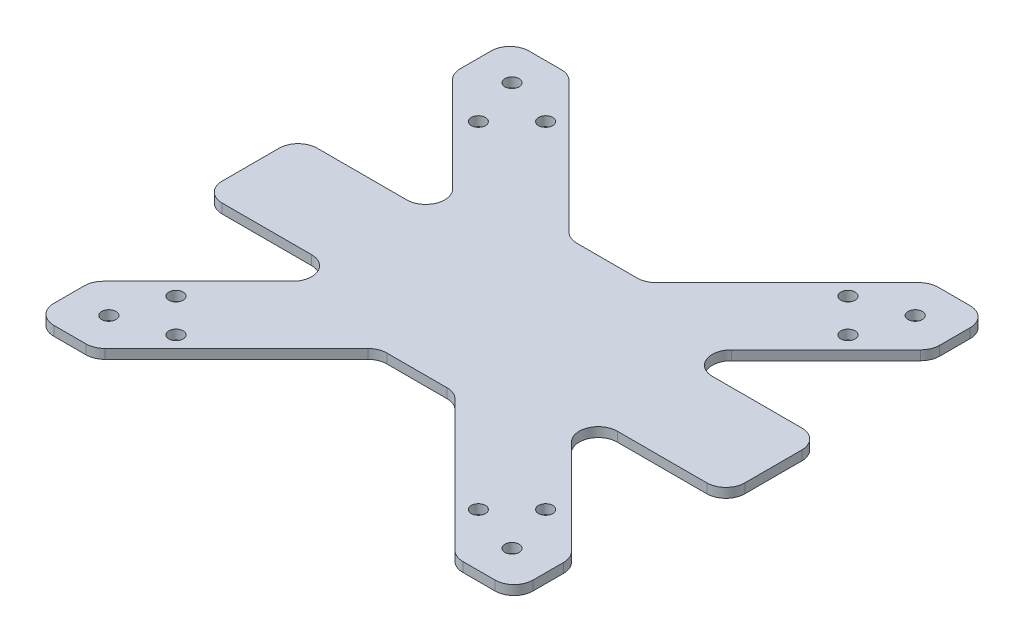
SolidWorks part; units mm, degrees
material "Thornel Mat VMA"
ref_plane "前视基准面" through (0, 0, 0) normal (0, 0, 1) x (1, 0, 0)
ref_plane "上视基准面" through (0, 0, 0) normal (0, 1, 0) x (1, 0, 0)
ref_plane "右视基准面" through (0, 0, 0) normal (1, 0, 0) x (0, 0, -1)
other "Configuration Table"
sketch "草图1" plane through (0, 0, 0) normal (0, 1, 0) x (1, 0, 0)
  line L1 (-60, -50) -> (60, -50)
  line L2 (-60, -50) -> (-60, 50)
  line L3 (-60, 50) -> (60, 50)
  line L4 (60, -50) -> (60, 50)
  line L5 (-60, -50) -> (60, 50) construction
  line L6 (-60, 50) -> (60, -50) construction
  point P0 (0, 0)
  dimension "D1" = 120
  dimension "D2" = 100
extrude "凸台-拉伸1" add sketch "草图1" along normal blind 2
sketch "草图3" plane through (0, 2, 0) normal (0, 1, 0) x (1, 0, 0)
  line L0 (-1000, 0) -> (49000, 0) construction
  line L1 (-42.4264, 42.4264) -> (0, 0) construction
  line L2 (-42.9749, 27.7358) -> (35312.3642, 35383.0749) construction
  line L3 (0, -1000) -> (0, 49000) construction
  circle A0 centre (0, 0) radius 60 construction
  circle A1 centre (-42.4264, 42.4264) radius 1.5
  circle A2 centre (-31.8198, 38.8909) radius 1.5
  circle A3 centre (-38.8909, 31.8198) radius 1.5
  circle A4 centre (-31.8198, -38.8909) radius 1.5
  circle A5 centre (-38.8909, -31.8198) radius 1.5
  circle A6 centre (-42.4264, -42.4264) radius 1.5
  circle A7 centre (31.8198, 38.8909) radius 1.5
  circle A8 centre (38.8909, 31.8198) radius 1.5
  circle A9 centre (42.4264, 42.4264) radius 1.5
  circle A10 centre (31.8198, -38.8909) radius 1.5
  circle A11 centre (42.4264, -42.4264) radius 1.5
  circle A12 centre (38.8909, -31.8198) radius 1.5
  dimension "D1" = 120
  dimension "D3" = 3
  dimension "D6" = 3
  dimension "D7" = 3
  dimension "D8" = 5
  dimension "D9" = 5
  dimension "D2" = 45
  dimension "D4" = 90
  dimension "D5" = 10
extrude "切除-拉伸2" cut sketch "草图3" against normal through all
sketch "草图4" plane through (0, 0, 0) normal (0, -1, 0) x (1, 0, 0)
  line L0 (-38, 50) -> (-8, 20)
  line L1 (-60, 50) -> (60, 50) construction
  line L2 (-8, 20) -> (8, 20)
  line L3 (8, 20) -> (38, 50)
  line L4 (38, 50) -> (-38, 50)
  line L5 (-1000, 0) -> (49000, 0) construction
  line L6 (8, -20) -> (38, -50)
  line L7 (-8, -20) -> (8, -20)
  line L8 (-38, -50) -> (-8, -20)
  line L9 (38, -50) -> (-38, -50)
  line L10 (0, -1000) -> (0, 49000) construction
  line L11 (-60, 47.5) -> (-20, 7.5)
  line L12 (-60, -50) -> (-60, 50) construction
  line L13 (-20, 7.5) -> (-20, -7.5)
  line L14 (-20, -7.5) -> (-60, -47.5)
  line L15 (-60, -47.5) -> (-60, 47.5)
  line L16 (20, -7.5) -> (60, -47.5)
  line L17 (20, 7.5) -> (20, -7.5)
  line L18 (60, 47.5) -> (20, 7.5)
  line L19 (60, -47.5) -> (60, 47.5)
  point P7 (0, 20)
  point P20 (-20, 0)
  dimension "D1" = 45
  dimension "D2" = 45
  dimension "D3" = 0
  dimension "D4" = 30
  dimension "D5" = 76
  dimension "D6" = 45
  dimension "D7" = 40
  dimension "D8" = 95
  dimension "D9" = 0
extrude "切除-拉伸3" cut sketch "草图4" against normal through all
sketch "草图7" plane through (0, 2, 0) normal (0, 1, 0) x (1, 0, 0)
  line L1 (-55, -10) -> (55, -10)
  line L2 (-55, -10) -> (-55, 10)
  line L3 (-55, 10) -> (55, 10)
  line L4 (55, -10) -> (55, 10)
  line L5 (-55, -10) -> (55, 10) construction
  line L6 (-55, 10) -> (55, -10) construction
  point P0 (0, 0)
  dimension "D1" = 20
  dimension "D2" = 110
extrude "凸台-拉伸3" add sketch "草图7" against normal blind 2
sketch "草图8" plane through (0, 0, 0) normal (0, -1, 0) x (1, 0, 0)
  line L0 (-1000, 0) -> (49000, 0) construction
  line L1 (-86.1328, 67.3807) -> (-50.4264, 67.3807)
  line L2 (-86.1328, 67.3807) -> (-86.1328, 30.5224)
  line L3 (-86.1328, 30.5224) -> (-50.4264, 30.5224)
  line L4 (-50.4264, 67.3807) -> (-50.4264, 30.5224)
  line L5 (0, -1000) -> (0, 49000) construction
  line L6 (-86.1328, -30.5224) -> (-50.4264, -30.5224)
  line L7 (-50.4264, -67.3807) -> (-50.4264, -30.5224)
  line L8 (-86.1328, -67.3807) -> (-50.4264, -67.3807)
  line L9 (-86.1328, -67.3807) -> (-86.1328, -30.5224)
  line L10 (86.1328, -67.3807) -> (86.1328, -30.5224)
  line L11 (86.1328, -67.3807) -> (50.4264, -67.3807)
  line L12 (50.4264, -67.3807) -> (50.4264, -30.5224)
  line L13 (86.1328, -30.5224) -> (50.4264, -30.5224)
  line L14 (86.1328, 30.5224) -> (50.4264, 30.5224)
  line L15 (50.4264, 67.3807) -> (50.4264, 30.5224)
  line L16 (86.1328, 67.3807) -> (50.4264, 67.3807)
  line L17 (86.1328, 67.3807) -> (86.1328, 30.5224)
  circle A1 centre (-42.4264, 42.4264) radius 1.5 construction
  dimension "D1" = 8
extrude "切除-拉伸5" cut sketch "草图8" against normal through all
fillet "圆角2" radius 4 24 edges at (-8, 1, -20) (8, 1, -20) (-8, 1, 20) (8, 1, 20) (-22.5, 1, 10) (-55, 1, 10) (-55, 1, -10) (-22.5, 1, -10) (-50.4264, 1, -37.9264) (-50.4264, 1, -50) (-38, 1, -50) (50.4264, 1, -37.9264) (38, 1, -50) (50.4264, 1, -50) (22.5, 1, 10) (22.5, 1, -10) (55, 1, 10) (55, 1, -10) (50.4264, 1, 37.9264) (50.4264, 1, 50) (38, 1, 50) (-38, 1, 50) (-50.4264, 1, 37.9264) (-50.4264, 1, 50)
